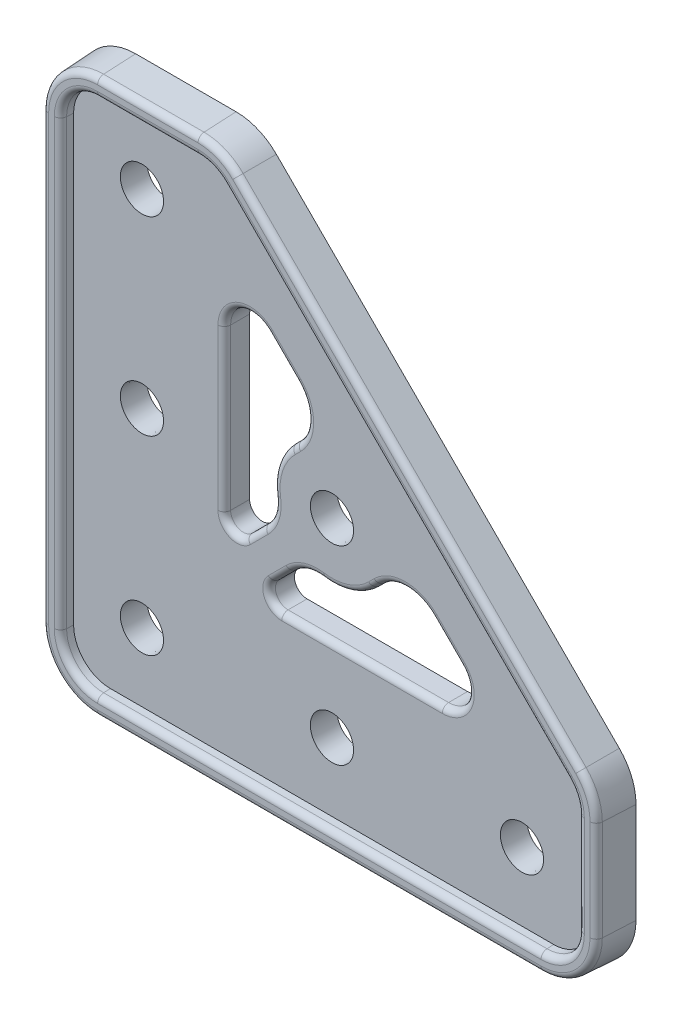
SolidWorks part; units mm, degrees
ref_plane "Front Plane" through (0, 0, 0) normal (0, 0, 1) x (1, 0, 0)
ref_plane "Top Plane" through (0, 0, 0) normal (0, 1, 0) x (1, 0, 0)
ref_plane "Right Plane" through (0, 0, 0) normal (1, 0, 0) x (0, 0, -1)
sketch "Sketch1" plane through (0, 0, 0) normal (0, 0, 1) x (1, 0, 0)
  line L0 (16.4645, 43.5355) -> (43.5355, 16.4645)
  line L1 (5, 0) -> (40, 0)
  line L2 (0, 5) -> (0, 40)
  line L3 (5, 45) -> (12.9289, 45)
  line L4 (45, 5) -> (45, 12.9289)
  arc A0 (0, 5) -> (5, 0) centre (5, 5) ccw
  arc A1 (45, 5) -> (40, 0) centre (40, 5) cw
  arc A2 (45, 12.9289) -> (43.5355, 16.4645) centre (40, 12.9289) ccw
  arc A3 (16.4645, 43.5355) -> (12.9289, 45) centre (12.9289, 40) ccw
  arc A4 (5, 45) -> (0, 40) centre (5, 40) ccw
  point P8 (0, 0)
  point P11 (45, 0)
  point P14 (45, 15)
  point P19 (0, 45)
  dimension "D4" = 5
  dimension "D1" = 45
  dimension "D2" = 45
  dimension "D3" = 15
extrude "Boss-Extrude1" add sketch "Sketch1" along normal blind 2 draft 3
sketch "Sketch2" plane through (0, 0, 2) normal (0, 0, 1) x (1, 0, 0)
  line L0 (7.5, 7.5) -> (58.6399, 7.5) construction
  line L2 (55, 0) -> (-55, 0) construction
  line L4 (7.5, 40) -> (7.5, 5)
  line L5 (7.5, 40) -> (7.5, 7.5) construction
  circle A0 centre (7.5, 37.5) radius 1.6
  circle A1 centre (7.5, 7.5) radius 1.6
  circle A2 centre (7.5, 22.5) radius 1.6
  circle A3 centre (22.5, 7.5) radius 1.6
  circle A4 centre (37.5, 7.5) radius 1.6
  dimension "D7" = 3.2
  dimension "D1" = 7.5
  dimension "D2" = 7.5
  dimension "D3" = 15
  dimension "D4" = 15
  dimension "D5" = 15
  dimension "D6" = 15
extrude "Cut-Extrude1" cut sketch "Sketch2" against normal blind 2
other "Move Face1" flip direction yes face at (2.0139, 2.0139, 1) face at (22.5, 0.0524, 1) face at (42.9861, 2.0139, 1) face at (44.9476, 8.9645, 1) face at (44.397, 14.7502, 1) face at (29.9629, 29.9629, 1) face at (14.7502, 44.397, 1) face at (8.9645, 44.9476, 1) face at (2.0139, 42.9861, 1) face at (0.0524, 22.5, 1) offset 0.5 parameters "D1"=0.5
sketch "Sketch3" plane through (0, 0, 2) normal (0, 0, 1) x (1, 0, 0)
  line L5 (5, 2.1055) -> (40, 2.1055)
  line L6 (42.8945, 5) -> (42.8945, 12.9289)
  line L7 (42.0467, 14.9757) -> (14.9757, 42.0467)
  line L8 (12.9289, 42.8945) -> (5, 42.8945)
  line L9 (2.1055, 40) -> (2.1055, 5)
  line L10 (5, 0.6055) -> (40, 0.6055)
  line L11 (44.3945, 5) -> (44.3945, 12.9289)
  line L12 (43.1074, 16.0363) -> (16.0363, 43.1074)
  line L13 (12.9289, 44.3945) -> (5, 44.3945)
  line L14 (0.6055, 40) -> (0.6055, 5)
  line L15 (5, 0.6055) -> (40, 0.6055)
  line L16 (44.3945, 5) -> (44.3945, 12.9289)
  line L17 (43.1074, 16.0363) -> (16.0363, 43.1074)
  line L18 (12.9289, 44.3945) -> (5, 44.3945)
  line L19 (0.6055, 40) -> (0.6055, 5)
  arc A5 (40, 2.1055) -> (42.8945, 5) centre (40, 5) ccw
  arc A6 (42.8945, 12.9289) -> (42.0467, 14.9757) centre (40, 12.9289) ccw
  arc A7 (14.9757, 42.0467) -> (12.9289, 42.8945) centre (12.9289, 40) ccw
  arc A8 (5, 42.8945) -> (2.1055, 40) centre (5, 40) ccw
  arc A9 (2.1055, 5) -> (5, 2.1055) centre (5, 5) ccw
  arc A10 (0.6055, 5) -> (5, 0.6055) centre (5, 5) ccw
  arc A11 (40, 0.6055) -> (44.3945, 5) centre (40, 5) ccw
  arc A12 (44.3945, 12.9289) -> (43.1074, 16.0363) centre (40, 12.9289) ccw
  arc A13 (16.0363, 43.1074) -> (12.9289, 44.3945) centre (12.9289, 40) ccw
  arc A14 (5, 44.3945) -> (0.6055, 40) centre (5, 40) ccw
  arc A15 (0.6055, 5) -> (5, 0.6055) centre (5, 5) ccw
  arc A16 (40, 0.6055) -> (44.3945, 5) centre (40, 5) ccw
  arc A17 (44.3945, 12.9289) -> (43.1074, 16.0363) centre (40, 12.9289) ccw
  arc A18 (16.0363, 43.1074) -> (12.9289, 44.3945) centre (12.9289, 40) ccw
  arc A19 (5, 44.3945) -> (0.6055, 40) centre (5, 40) ccw
  dimension "D2" = 1.5
  dimension "D1" = 0
extrude "Boss-Extrude2" add sketch "Sketch3" along normal blind 1 draft 3
fillet "Fillet1" radius 0.5 20 edges at (42.0838, 2.9162, 3) (42.9469, 8.9645, 3) (42.7226, 14.0567, 3) (28.5482, 28.5482, 3) (14.0567, 42.7226, 3) (8.9645, 42.9469, 3) (2.9162, 42.0838, 3) (2.0531, 22.5, 3) (2.9162, 2.9162, 3) (22.5, 2.0531, 3) (0.6579, 22.5, 3) (1.9297, 43.0703, 3) (8.9645, 44.3421, 3) (14.5906, 44.0116, 3) (29.5348, 29.5348, 3) (44.0116, 14.5906, 3) (44.3421, 8.9645, 3) (43.0703, 1.9297, 3) (22.5, 0.6579, 3) (1.9297, 1.9297, 3)
sketch "Sketch7" plane through (0, 0, 2) normal (0, 0, 1) x (1, 0, 0)
  line L0 (7.5, 37.5) -> (37.5, 7.5) construction
  circle A0 centre (22.5, 22.5) radius 1.6
  circle A1 centre (7.5, 37.5) radius 1.6 construction
extrude "Cut-Extrude4" cut sketch "Sketch7" against normal through all
sketch "Sketch5" plane through (0, 0, 2) normal (0, 0, 1) x (1, 0, 0)
  line L0 (14, 31.2042) -> (14, 18.5355)
  line L1 (18.5355, 14) -> (31.2042, 14)
  line L2 (32.638, 17.4615) -> (30.4238, 19.6758)
  line L3 (42.0467, 14.9757) -> (14.9757, 42.0467) construction
  line L4 (0, -54.6431) -> (0, 54.6431) construction
  line L5 (55, 0) -> (-55, 0) construction
  line L6 (43.1815, 16.1104) -> (16.1104, 43.1815) construction
  line L7 (19.2473, 25.7527) -> (19.6758, 26.1811)
  line L8 (25.7527, 19.2473) -> (26.1811, 19.6758)
  line L9 (19.6758, 30.4238) -> (17.4615, 32.638)
  line L10 (22.5, 22.5) -> (7.5, 7.5) construction
  line L11 (15.7071, 17.8284) -> (17.1086, 19.23)
  line L12 (17.8284, 15.7071) -> (19.23, 17.1086)
  arc A0 (21.8047, 17.9528) -> (25.7527, 19.2473) centre (22.5, 22.5) ccw
  arc A1 (31.2042, 14) -> (32.638, 17.4615) centre (31.2042, 16.0277) ccw
  arc A2 (17.4615, 32.638) -> (14, 31.2042) centre (16.0277, 31.2042) ccw
  arc A4 (26.1811, 19.6758) -> (30.4238, 19.6758) centre (28.3025, 17.5544) cw
  circle A5 centre (22.5, 22.5) radius 4.6
  arc A6 (19.2473, 25.7527) -> (17.9528, 21.8047) centre (22.5, 22.5) ccw
  arc A7 (19.6758, 26.1811) -> (19.6758, 30.4238) centre (17.5544, 28.3025) ccw
  arc A8 (21.8047, 17.9528) -> (19.23, 17.1086) centre (21.3513, 14.9873) ccw
  arc A9 (17.9528, 21.8047) -> (17.1086, 19.23) centre (14.9873, 21.3513) cw
  arc A10 (14, 18.5355) -> (15.7071, 17.8284) centre (15, 18.5355) ccw
  arc A11 (18.5355, 14) -> (17.8284, 15.7071) centre (18.5355, 15) cw
  point P27 (21.7971, 28.3025)
  point P32 (20.4858, 18.3644)
  dimension "D4" = 3
  dimension "D6" = 3
  dimension "D8" = 1
  dimension "D9" = 1
  dimension "D1" = 14
  dimension "D2" = 14
  dimension "D3" = 6.5
  dimension "D7" = 3
  dimension "D5" = 3
extrude "Cut-Extrude2" cut sketch "Sketch5" against normal through all
fillet "Fillet3" radius 0.5 18 edges at (17.6117, 14.6173, 2) (18.5292, 16.4079, 2) (20.4166, 17.838, 2) (23.9332, 18.129, 2) (25.9669, 19.4615, 2) (28.3025, 20.5544, 2) (31.5309, 18.5687, 2) (33.0775, 15.2518, 2) (16.4079, 18.5292, 2) (14.6173, 17.6117, 2) (14, 24.8698, 2) (15.2518, 33.0775, 2) (18.5687, 31.5309, 2) (20.5544, 28.3025, 2) (19.4615, 25.9669, 2) (18.129, 23.9332, 2) (24.8698, 14, 2) (17.838, 20.4166, 2)
sketch "Sketch6" plane through (0, 0, 0) normal (0, 0, -1) x (-1, 0, 0)
  line L0 (-44.7584, 10.9979) -> (-10.2693, 45.4871) construction
  line L1 (-43.1815, 16.1104) -> (-16.1104, 43.1815) construction
  line L2 (-39.1919, 18.6858) -> (-18.6858, 39.1919)
  line L3 (-17.9787, 39.1919) -> (-16.5645, 37.7777)
  line L4 (-16.5645, 37.0706) -> (-37.0706, 16.5645)
  line L5 (-37.7777, 16.5645) -> (-39.1919, 17.9787)
  line L6 (-22.5, 22.5) -> (-29.5523, 29.5523) construction
  line L8 (-16.0168, 43.0879) -> (-43.0879, 16.0168) construction
  arc A0 (-39.1919, 18.6858) -> (-39.1919, 17.9787) centre (-38.8383, 18.3323) ccw
  arc A1 (-37.0706, 16.5645) -> (-37.7777, 16.5645) centre (-37.4241, 16.918) cw
  arc A2 (-16.5645, 37.7777) -> (-16.5645, 37.0706) centre (-16.918, 37.4241) cw
  arc A3 (-18.6858, 39.1919) -> (-17.9787, 39.1919) centre (-18.3323, 38.8383) cw
  point P12 (-37.4241, 16.2109)
  point P15 (-16.2109, 37.4241)
  point P18 (-18.3323, 39.5455)
  dimension "D3" = 0.5
  dimension "D1" = 30
  dimension "D2" = 3
  dimension "D4" = 1
extrude "Cut-Extrude3" cut sketch "Sketch6" against normal blind 0.2 draft 3
draft "Draft1" type of draft neutral plane draft angle 3 faces to draft 6 face at (24.1, 22.5, 0) face at (39.1, 7.5, 0) face at (24.1, 7.5, 0) face at (9.1, 7.5, 0) face at (9.1, 22.5, 0) face at (9.1, 37.5, 0) neutral plane through (5, 5, 0) neutral plane normal (0, 0, -1) reverse direction yes parameters "D1"=3
sketch "Alignment_Sketch" [suppressed] plane through (0, 0, 0) normal (0, 0, -1) x (-1, 0, 0)
  line L0 (-7.5, 37.5) -> (-7.5, 7.5) construction
  line L1 (-7.5, 7.5) -> (-37.5, 7.5) construction
  line L2 (-37.5, 7.5) -> (-7.5, 37.5) construction
  point P0 (-7.5, 37.5)
  point P1 (-7.5, 7.5)
  point P3 (-22.5, 7.5)
  point P5 (-37.5, 7.5)
  point P7 (-22.5, 22.5)
  point P9 (-7.5, 22.5)
